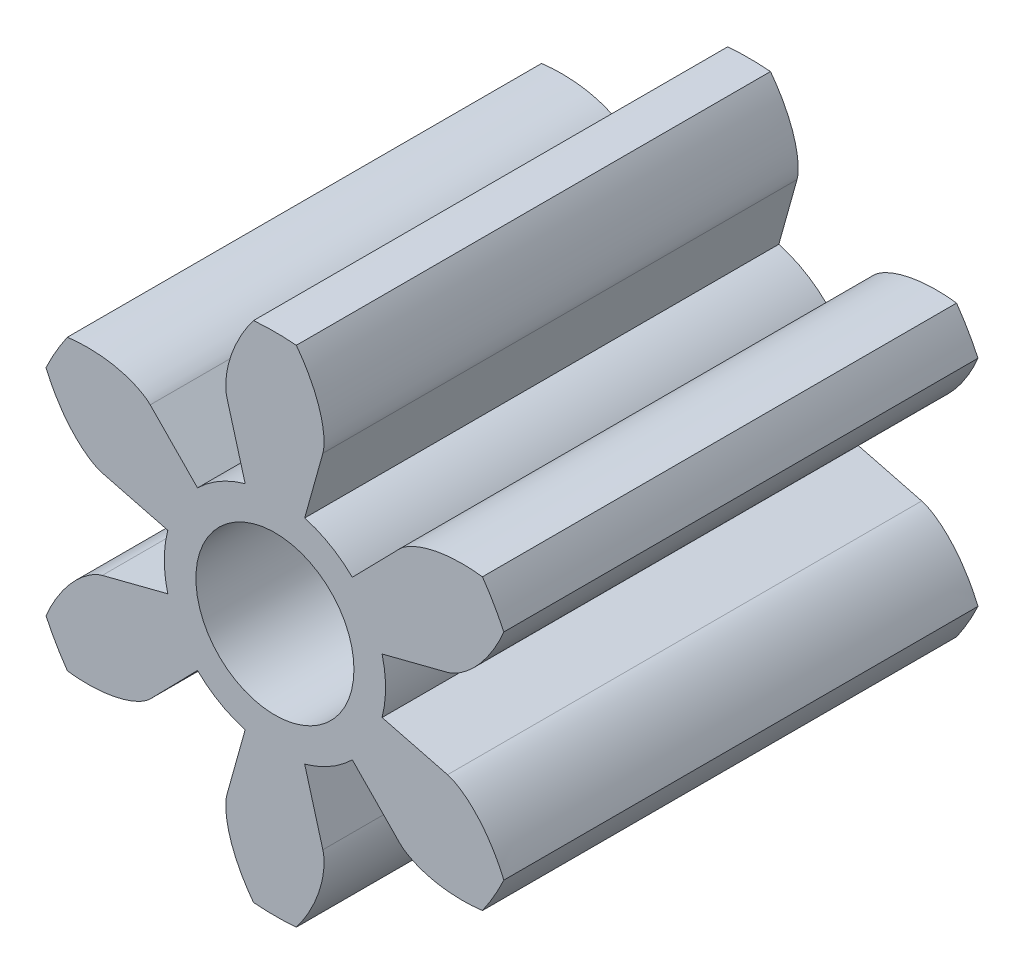
SolidWorks part; units mm, degrees
ref_plane "前视基准面" through (0, 0, 0) normal (0, 0, 1) x (1, 0, 0)
ref_plane "上视基准面" through (0, 0, 0) normal (0, 1, 0) x (1, 0, 0)
ref_plane "右视基准面" through (0, 0, 0) normal (1, 0, 0) x (0, 0, -1)
other "Configuration Table"
sketch "草图1" plane through (0, 0, 0) normal (0, 0, 1) x (1, 0, 0)
  line L0 (0, 0) -> (1.2, 0) construction
  line L1 (0, 0) -> (1.1591, 0.3106) construction
  line L2 (0, 0) -> (1.0922, 0.2804)
  line L3 (1.1591, 0.3106) -> (1.1591, -0.3106) construction
  line L4 (0, 0) -> (1.0922, -0.2804)
  circle A0 centre (0, 0) radius 1.6
  circle A1 centre (0, 0) radius 1.2 construction
  circle A2 centre (0, 0) radius 0.7
  circle A3 centre (0, 0) radius 1.1276 construction
  circle A4 centre (0, 0) radius 0.5
  spline S0 degree 4 poles (1.0922, 0.2804) (1.1005, 0.2825) (1.1233, 0.2902) (1.1642, 0.3116) (1.2251, 0.355) (1.2944, 0.4229) (1.3701, 0.5218) (1.4405, 0.6499) (1.4968, 0.8001) (1.5346, 0.9688) (1.5512, 1.1408) (1.5483, 1.3135) (1.5263, 1.4934) (1.476, 1.7121) (1.3831, 1.9634) (1.2333, 2.2367) (1.0225, 2.5109) (0.7738, 2.7518) (0.4963, 2.957) (0.1928, 3.1247) (-0.1252, 3.2551) (-0.4618, 3.3464) (-0.7968, 3.4019) (-1.1526, 3.4175) (-1.4209, 3.4059) (-1.7199, 3.3653) (-1.8885, 3.3305) (-2.0792, 3.2854) (-2.1801, 3.2512) (-2.2647, 3.2261) (-2.2887, 3.2165) (-2.3068, 3.2104) knots 0 0 0 0 0 0.005604 0.015718 0.02996 0.048734 0.068727 0.096889 0.125051 0.153212 0.181374 0.209535 0.237696 0.271429 0.327752 0.384075 0.440398 0.496721 0.553044 0.609367 0.66569 0.722013 0.778336 0.834659 0.890982 0.909091 0.954545 0.977273 0.988636 1 1 1 1 1 construction
  spline S1 degree 4 poles (1.0922, 0.2804) (1.1005, 0.2825) (1.1233, 0.2902) (1.1642, 0.3116) (1.2251, 0.355) (1.2944, 0.4229) (1.3701, 0.5218) (1.4405, 0.6499) (1.4968, 0.8001) (1.5346, 0.9688) (1.5512, 1.1408) (1.5483, 1.3135) (1.5263, 1.4934) (1.476, 1.7121) (1.3831, 1.9634) (1.2333, 2.2367) (1.0225, 2.5109) (0.7738, 2.7518) (0.4963, 2.957) (0.1928, 3.1247) (-0.1252, 3.2551) (-0.4618, 3.3464) (-0.7968, 3.4019) (-1.1526, 3.4175) (-1.4209, 3.4059) (-1.6427, 3.3757) (-1.7453, 3.358) (-1.77, 3.3534) knots 0 0 0 0 0 0.005604 0.015718 0.02996 0.048734 0.068727 0.096889 0.125051 0.153212 0.181374 0.209535 0.237696 0.271429 0.327752 0.384075 0.440398 0.496721 0.553044 0.609367 0.66569 0.722013 0.778336 0.834659 0.890982 0.909091 0.909091 0.909091 0.909091 0.909091
  spline S2 degree 4 poles (1.0922, -0.2804) (1.1005, -0.2825) (1.1233, -0.2902) (1.1642, -0.3116) (1.2251, -0.355) (1.2944, -0.4229) (1.3701, -0.5218) (1.4405, -0.6499) (1.4968, -0.8001) (1.5346, -0.9688) (1.5512, -1.1408) (1.5483, -1.3135) (1.5263, -1.4934) (1.476, -1.7121) (1.3831, -1.9634) (1.2333, -2.2367) (1.0225, -2.5109) (0.7738, -2.7518) (0.4963, -2.957) (0.1928, -3.1247) (-0.1252, -3.2551) (-0.4618, -3.3464) (-0.7968, -3.4019) (-1.1526, -3.4175) (-1.4209, -3.4059) (-1.7199, -3.3653) (-1.8885, -3.3305) (-2.0792, -3.2854) (-2.1801, -3.2512) (-2.2647, -3.2261) (-2.2887, -3.2165) (-2.3068, -3.2104) knots 0 0 0 0 0 0.005604 0.015718 0.02996 0.048734 0.068727 0.096889 0.125051 0.153212 0.181374 0.209535 0.237696 0.271429 0.327752 0.384075 0.440398 0.496721 0.553044 0.609367 0.66569 0.722013 0.778336 0.834659 0.890982 0.909091 0.954545 0.977273 0.988636 1 1 1 1 1 construction
  spline S3 degree 4 poles (1.0922, -0.2804) (1.1005, -0.2825) (1.1233, -0.2902) (1.1642, -0.3116) (1.2251, -0.355) (1.2944, -0.4229) (1.3701, -0.5218) (1.4405, -0.6499) (1.4968, -0.8001) (1.5346, -0.9688) (1.5512, -1.1408) (1.5483, -1.3135) (1.5263, -1.4934) (1.476, -1.7121) (1.3831, -1.9634) (1.2333, -2.2367) (1.0225, -2.5109) (0.7738, -2.7518) (0.4963, -2.957) (0.1928, -3.1247) (-0.1252, -3.2551) (-0.4618, -3.3464) (-0.7968, -3.4019) (-1.1526, -3.4175) (-1.4209, -3.4059) (-1.6427, -3.3757) (-1.7453, -3.358) (-1.77, -3.3534) knots 0 0 0 0 0 0.005604 0.015718 0.02996 0.048734 0.068727 0.096889 0.125051 0.153212 0.181374 0.209535 0.237696 0.271429 0.327752 0.384075 0.440398 0.496721 0.553044 0.609367 0.66569 0.722013 0.778336 0.834659 0.890982 0.909091 0.909091 0.909091 0.909091 0.909091
  point P15 (1.1591, 0)
  dimension "齿顶圆直径" = 3.2
  dimension "分度圆直径" = 2.4
  dimension "齿根圆直径" = 1.4
  dimension "基圆直径" = 2.2553
  dimension "内孔直径" = 1
  dimension "渐近线镜像线夹角" = 15
extrude "凸台-拉伸1" add sketch "草图1" along normal blind 3 contours A0 | A4
extrude "切除-拉伸1" cut sketch "草图1<3>" along normal through all contours A2 S3 A0 S1 region at (1.2301, 0, 0)
sketch "草图1<3>" plane through (0, 0, 0) normal (0, 0, 1) x (1, 0, 0) same geometry as "草图1"
pattern_circular "阵列(圆周)1" count 6 every 60 about axis through (0, 0, 3) along (0, 0, 1) of "切除-拉伸1"
equation "\"m\"= 0.4'模数"
equation "\"z\" = 6'齿数"
equation "\"a\"= 20度'压力角"
equation "\"d\"= \"m\" * \"z\"'分度圆直径"
equation "\"da\"= ( \"z\" + 2 ) * \"m\"'齿顶圆直径"
equation "\"df\"= ( \"z\" - 2.5 ) * \"m\"'齿根圆直径"
equation "\"s\"= 0.5 * PI * \"m\"'分度圆齿厚"
equation "\"r\"= 0.38 * \"m\"'齿根圆角"
equation "\"B\"= 0.3 * \"d\"'齿厚"
equation "\"db\"= \"m\" * \"z\" * cos ( \"a\" )'基圆直径"
equation "\"rb\"= \"db\" / 2'基圆半径"
equation "\"齿顶圆直径@草图1\"= \"da\""
equation "\"分度圆直径@草图1\"= \"d\""
equation "\"齿根圆直径@草图1\"= \"df\""
equation "\"基圆直径@草图1\"= \"db\""
equation "\"渐近线镜像线夹角@草图1\"= 360 / 4 / \"z\""
equation "\"h\" = 3'齿轮厚度"
equation "\"ir\"= 1'内孔直径"
equation "\"内孔直径@草图1\"= \"ir\""
equation "\"齿轮厚@凸台-拉伸1\"= \"h\""
equation "\"齿轮夹角@阵列(圆周)1\"= 360 / \"z\""
equation "\"齿数@阵列(圆周)1\"= \"z\""
